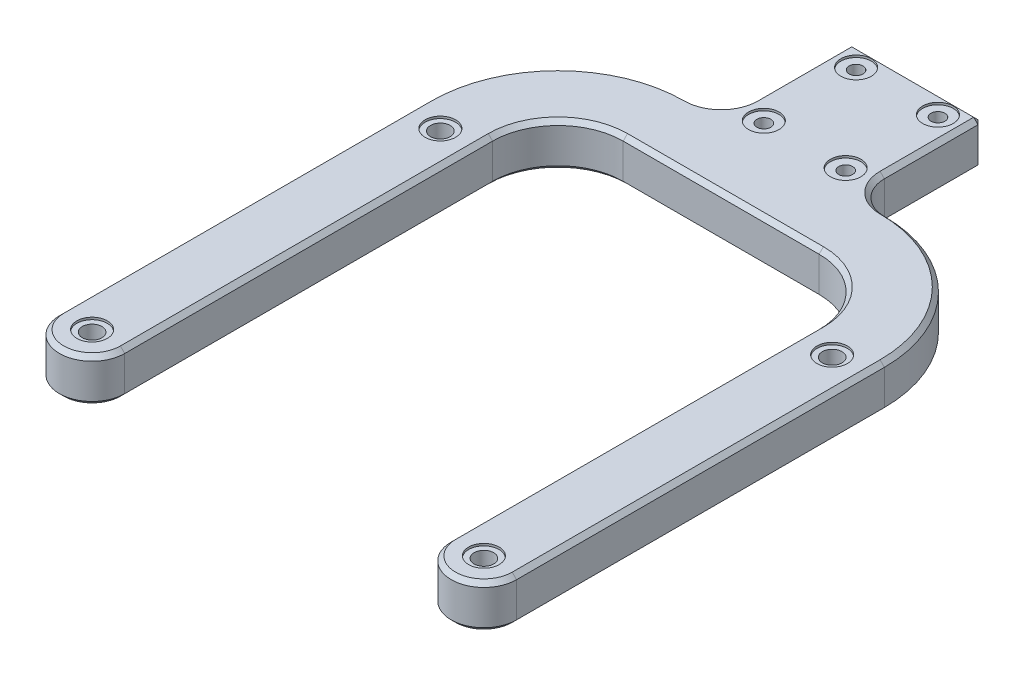
SolidWorks part; units mm, degrees
material "ABS PC"
ref_plane "Front Plane" through (0, 0, 0) normal (0, 0, 1) x (1, 0, 0)
ref_plane "Top Plane" through (0, 0, 0) normal (0, 1, 0) x (1, 0, 0)
ref_plane "Right Plane" through (0, 0, 0) normal (1, 0, 0) x (0, 0, -1)
sketch "Sketch1" plane through (0, 0, 0) normal (0, 1, 0) x (1, 0, 0)
  line L0 (22.5, 57.25) -> (0, 57.25)
  line L1 (0, 57.25) -> (0, 102.25)
  line L2 (37.5, 42.25) -> (37.5, -42.25)
  line L7 (15, 102.25) -> (0, 102.25)
  line L8 (0, 0) -> (0, 57.25) construction
  line L9 (15, 102.25) -> (15, 72.25)
  line L13 (15, 72.25) -> (22.5, 72.25)
  line L14 (52.5, 42.25) -> (52.5, -42.25)
  arc A4 (22.5, 57.25) -> (37.5, 42.25) centre (22.5, 42.25) cw
  arc A6 (22.5, 72.25) -> (52.5, 42.25) centre (22.5, 42.25) cw
  circle A7 centre (9.4, 97.65) radius 1.6
  circle A8 centre (9.4, 76.45) radius 1.6
  arc A9 (37.5, -42.25) -> (52.5, -42.25) centre (45, -42.25) ccw
  circle A10 centre (45, 37.75) radius 2.25
  circle A11 centre (45, -42.25) radius 2.25
  point P10 (37.5, 0)
  dimension "D7" = 80
  dimension "D8" = 30
  dimension "D9" = 15
  dimension "D10" = 3.2
  dimension "D11" = 18
  dimension "D12" = 3
  dimension "D13" = 4
  dimension "D6" = 107
  dimension "D14" = 4.5
  dimension "D1" = 15
  dimension "D2" = 15
  dimension "D3" = 30
  dimension "D4" = 30
  dimension "D5" = 75
extrude "Boss-Extrude1" add sketch "Sketch1" along normal blind 10
sketch "Sketch4" plane through (0, 10, 0) normal (0, 1, 0) x (1, 0, 0)
  circle A0 centre (9.4, 97.65) radius 3.5
  circle A1 centre (9.4, 76.45) radius 3.5
  circle A2 centre (45, 37.75) radius 3.5
  circle A3 centre (45, -42.25) radius 3.5
  dimension "D1" = 7
extrude "Cut-Extrude1" cut sketch "Sketch4" against normal blind 0.5
fillet "Fillet1" radius 7.5 1 edges at (15, 5, -72.25)
chamfer "Chamfer1" distance 1 angle 45 19 edges at (11.25, 0, -57.25) (33.1066, 0, -52.8566) (37.5, 0, 0) (52.5, 0, 0) (43.7132, 0, -63.4632) (15, 0, -91) (7.5, 0, -102.25) (11.25, 10, -57.25) (33.1066, 10, -52.8566) (37.5, 10, 0) (52.5, 10, 0) (43.7132, 10, -63.4632) (15, 10, -91) (7.5, 10, -102.25) (17.1967, 0, -74.4467) (17.1967, 10, -74.4467) (15, 5, -102.25) (45, 0, 49.75) (45, 10, 49.75)
sketch "Sketch5" plane through (0, 0, 0) normal (0, -1, 0) x (1, 0, 0)
  circle A0 centre (45, -37.75) radius 2.25 construction
  circle A1 centre (45, 42.25) radius 2.25 construction
  circle A2 centre (45, -37.75) radius 2.25
  circle A3 centre (45, 42.25) radius 2.25
extrude "Boss-Extrude2" add sketch "Sketch5" against normal offset from surface (4 mm away) 6 up to face at (9.4, 10, -94.15)
mirror "Mirror1" about plane through (0, 10, -57.25) normal (1, 0, 0) of bodies 104 101
